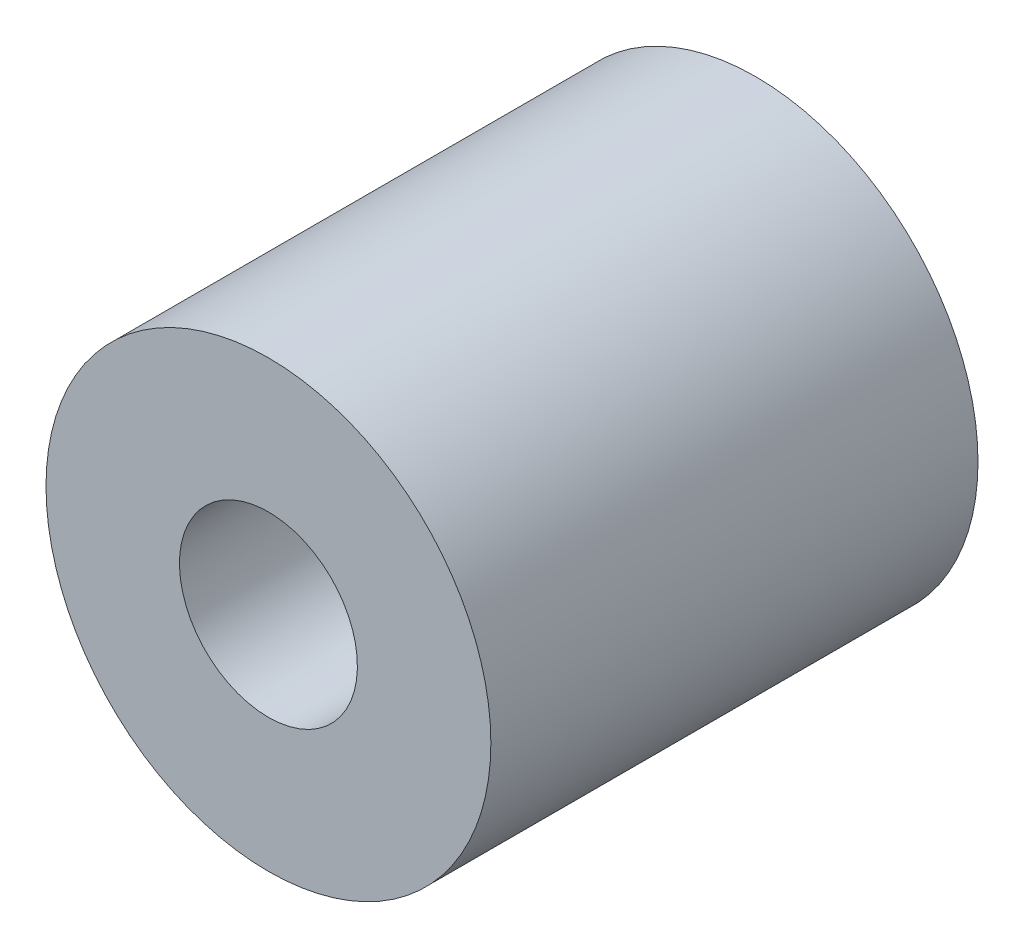
SolidWorks part; units mm, degrees
ref_plane "Front Plane" through (0, 0, 0) normal (0, 0, 1) x (1, 0, 0)
ref_plane "Top Plane" through (0, 0, 0) normal (0, 1, 0) x (1, 0, 0)
ref_plane "Right Plane" through (0, 0, 0) normal (1, 0, 0) x (0, 0, -1)
sketch "Sketch1" plane through (0, 0, 0) normal (0, 0, 1) x (1, 0, 0)
  circle A0 centre (-70, 14.1421) radius 3 construction
  circle A1 centre (-70, 14.1421) radius 3
  circle A2 centre (-70, 14.1421) radius 7.5
  arc A3 (-70, 21.6421) -> (-72.9354, 7.2405) centre (-70, 14.1421) ccw construction
extrude "Boss-Extrude1" add sketch "Sketch1" along normal up to surface (16.425 mm away)
